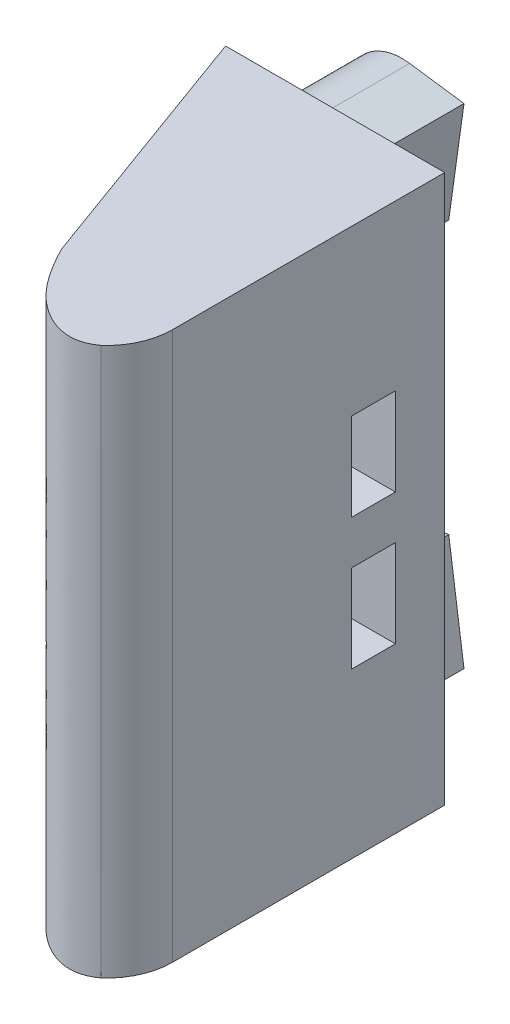
SolidWorks part; units mm, degrees
ref_plane "Front Plane" through (0, 0, 0) normal (0, 0, 1) x (1, 0, 0)
ref_plane "Top Plane" through (0, 0, 0) normal (0, 1, 0) x (1, 0, 0)
ref_plane "Right Plane" through (0, 0, 0) normal (1, 0, 0) x (0, 0, -1)
sketch "Sketch1" plane through (0, 0, 0) normal (0, 1, 0) x (1, 0, 0)
  line L0 (0, 0) -> (20, 0)
  line L1 (20, 0) -> (20, -24.8557)
  line L2 (0, 0) -> (8.5505, -23.4923)
  arc A0 (20, -24.8557) -> (17.9736, -29.3468) centre (14.01, -24.8557) cw
  spline S0 degree 3 poles (17.9736, -29.3468) (16.2811, -30.6017) (11.8764, -29.3199) (9.5982, -25.5616) (8.5505, -23.4923) knots 0 0 0 0 0.430743 1 1 1 1
  point P8 (20, -30)
  dimension "D5" = 5.99
  dimension "D6" = 25
  dimension "D1" = 30
  dimension "D3" = 20
  dimension "D4" = 70
extrude "Boss-Extrude1" add sketch "Sketch1" along normal blind 50 contours L2 A0 L1 L0 region at (12.3352, 0, 12.7005)
sketch "Sketch2" plane through (0, 0, 0) normal (0, 0, -1) x (-1, 0, 0)
  line L0 (-20, 25) -> (0, 25) construction
  line L1 (-20, 50) -> (-20, 0) construction
  line L2 (0, 50) -> (0, 0) construction
  circle A0 centre (-14, 31) radius 1.6
  circle A1 centre (-14, 19) radius 1.6
  dimension "D1" = 3.2
  dimension "D2" = 6
  dimension "D3" = 6
extrude "Cut-Extrude1" cut sketch "Sketch2" against normal blind 20
sketch "Sketch4" plane through (20, 0, 0) normal (1, 0, 0) x (0, 0, -1)
  line L0 (0, 25) -> (-24.8557, 25) construction
  line L1 (0, 50) -> (0, 0) construction
  line L2 (-24.8557, 50) -> (-24.8557, 0) construction
  line L3 (-4.5, 15) -> (-8.5, 15)
  line L4 (-4.5, 27) -> (-8.5, 27)
  line L5 (-4.5, 27) -> (-4.5, 35)
  line L6 (-4.5, 35) -> (-8.5, 35)
  line L7 (-8.5, 27) -> (-8.5, 35)
  line L8 (-8.5, 23) -> (-8.5, 15)
  line L9 (-4.5, 23) -> (-8.5, 23)
  line L10 (-4.5, 23) -> (-4.5, 15)
  point P10 (-4.5, 31)
  point P11 (-6.5, 27)
  dimension "D1" = 6
  dimension "D2" = 6.5
  dimension "D3" = 8
  dimension "D4" = 4
extrude "Cut-Extrude2" cut sketch "Sketch4" against normal blind 12
sketch "Sketch5" plane through (0, 0, 0) normal (0, 0, -1) x (-1, 0, 0)
  line L0 (-20, 25) -> (0, 25) construction
  line L1 (-20, 50) -> (-20, 0) construction
  line L2 (0, 50) -> (0, 0) construction
  line L3 (-14, 31) -> (-20, 73.6922) construction
  line L4 (-14, 31) -> (-14.835, 36.9416) construction
  line L5 (-14.835, 36.9416) -> (-11.3691, 37.4287) construction
  line L6 (-11.3691, 37.4287) -> (-12.7608, 47.3314)
  line L7 (-11.3691, 37.4287) -> (-1.4664, 38.8204)
  line L8 (-1.4664, 38.8204) -> (-2.8582, 48.7231)
  line L9 (-2.8582, 48.7231) -> (-12.7608, 47.3314)
  line L10 (-11.3691, 12.5713) -> (-12.7608, 2.6686)
  line L11 (-2.8582, 1.2769) -> (-12.7608, 2.6686)
  line L12 (-1.4664, 11.1796) -> (-2.8582, 1.2769)
  line L13 (-11.3691, 12.5713) -> (-1.4664, 11.1796)
  dimension "D1" = 8
  dimension "D2" = 6
  dimension "D3" = 90
  dimension "D4" = 3.5
  dimension "D5" = 90
  dimension "D6" = 10
  dimension "D7" = 10
extrude "Boss-Extrude2" add sketch "Sketch5" along normal blind 9
fillet "Fillet1" radius 5 1 edges at (2.8582, 48.7231, -4.5)
fillet "Fillet3" radius 5 1 edges at (1.4664, 38.8204, -4.5)
fillet "Fillet4" radius 5 2 edges at (2.8582, 1.2769, -4.5) (1.4664, 11.1796, -4.5)
sketch "Sketch6" plane through (0, 0, 0) normal (0, 0, -1) x (-1, 0, 0)
  line L0 (-20, 25) -> (0, 25) construction
  line L1 (-20, 50) -> (-20, 0) construction
  line L2 (0, 50) -> (0, 0) construction
  circle A0 centre (-14, 31) radius 2.5
  circle A1 centre (-14, 31) radius 1.6
  circle A2 centre (-14, 19) radius 2.5
  circle A3 centre (-14, 19) radius 1.6
  dimension "D1" = 5
extrude "Boss-Extrude3" add sketch "Sketch6" along normal blind 1
